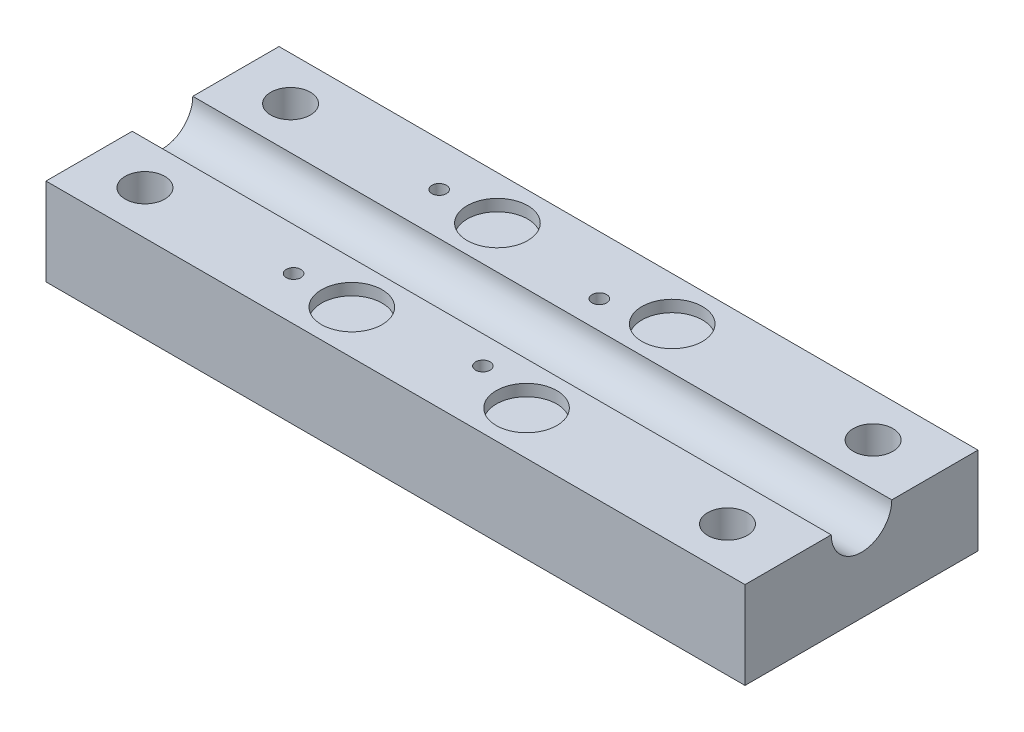
SolidWorks part; units mm, degrees
ref_plane "Front Plane" through (0, 0, 0) normal (0, 0, 1) x (1, 0, 0)
ref_plane "Top Plane" through (0, 0, 0) normal (0, 1, 0) x (1, 0, 0)
ref_plane "Right Plane" through (0, 0, 0) normal (1, 0, 0) x (0, 0, -1)
sketch "Sketch1" plane through (0, 0, 0) normal (0, 1, 0) x (1, 0, 0)
  line L1 (-38.1, 12.7) -> (38.1, 12.7)
  line L2 (-38.1, 12.7) -> (-38.1, -12.7)
  line L3 (-38.1, -12.7) -> (38.1, -12.7)
  line L4 (38.1, 12.7) -> (38.1, -12.7)
  dimension "D1" = 25.4
  dimension "D2" = 76.2
  dimension "D3" = 38.1
  dimension "D4" = 12.7
extrude "Boss-Extrude1" add sketch "Sketch1" along normal blind 9.525
sketch "Sketch2" plane through (0, 9.525, 0) normal (0, 1, 0) x (1, 0, 0)
  circle A0 centre (-32.0741, 7.9375) radius 2.159
  circle A1 centre (-32.0741, -7.9375) radius 2.159
  circle A2 centre (31.4259, 7.9375) radius 2.159
  circle A3 centre (31.4259, -7.9375) radius 2.159
  dimension "D1" = 4.318
  dimension "D2" = 15.875
  dimension "D3" = 63.5
  dimension "D4" = 32.0741
  dimension "D5" = 7.9375
extrude "Cut-Extrude1" cut sketch "Sketch2" against normal through all
sketch "Sketch3" plane through (0, 9.525, 0) normal (0, 1, 0) x (1, 0, 0)
  circle A0 centre (-9.525, 7.9375) radius 3.302
  circle A1 centre (-9.525, -7.9375) radius 3.302
  circle A2 centre (9.525, -7.9375) radius 3.302
  circle A3 centre (9.525, 7.9375) radius 3.302
  dimension "D1" = 6.604
  dimension "D2" = 15.875
  dimension "D3" = 19.05
  dimension "D4" = 7.9375
  dimension "D5" = 9.525
extrude "Cut-Extrude2" cut sketch "Sketch3" against normal blind 1.27
sketch "Sketch4" plane through (0, 9.525, 0) normal (0, 1, 0) x (1, 0, 0)
  circle A0 centre (-15.875, 7.9375) radius 0.7937
  circle A1 centre (-15.875, -7.9375) radius 0.7937
  circle A2 centre (3.175, 6.35) radius 0.7937
  circle A3 centre (3.175, -6.35) radius 0.7938
  point P10 (-7.2541, -5.2757)
  dimension "D1" = 1.5875
  dimension "D2" = 15.875
  dimension "D3" = 7.9375
  dimension "D4" = 15.875
  dimension "D5" = 12.7
  dimension "D6" = 6.35
  dimension "D7" = 3.175
extrude "Cut-Extrude3" cut sketch "Sketch4" against normal through all
sketch "Sketch5" plane through (-38.1, 0, 0) normal (-1, 0, 0) x (0, 0, 1)
  line L0 (-12.7, 9.525) -> (12.7, 9.525) construction
  circle A0 centre (0, 9.525) radius 3.302
  dimension "D1" = 6.604
extrude "Cut-Extrude4" cut sketch "Sketch5" against normal through all
